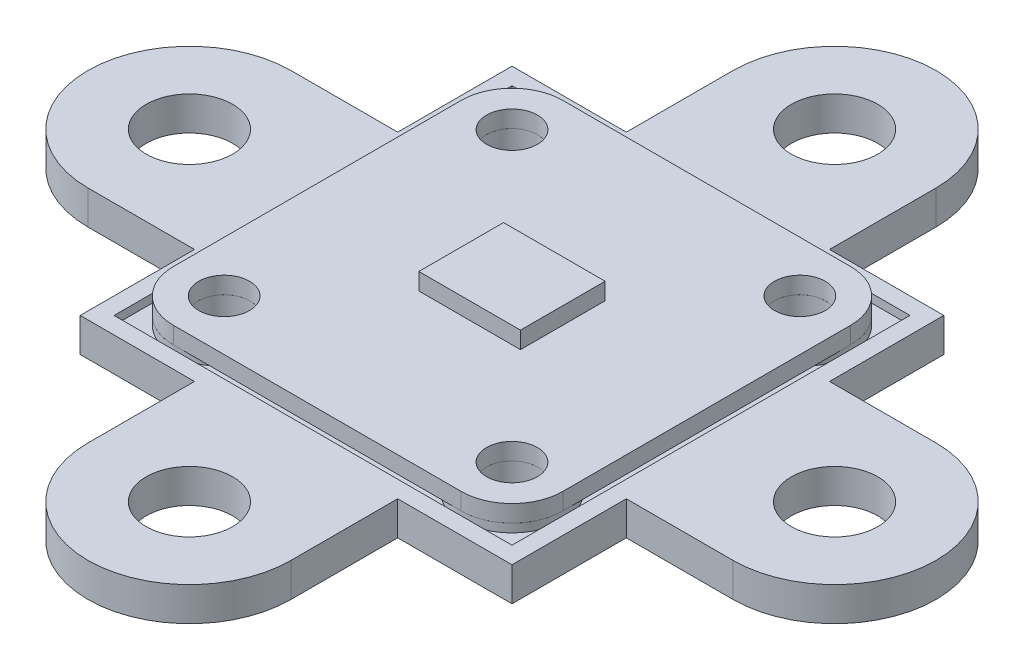
SolidWorks part; units mm, degrees
ref_plane "Front Plane" through (0, 0, 0) normal (0, 0, 1) x (1, 0, 0)
ref_plane "Top Plane" through (0, 0, 0) normal (0, 1, 0) x (1, 0, 0)
ref_plane "Right Plane" through (0, 0, 0) normal (1, 0, 0) x (0, 0, -1)
other "Bounding Box"
ref_plane "Default Plane" through (-8.9266, -12.7485, 0) normal (-0.1736, 0.9848, 0) x (0.9848, 0.1736, 0)
sketch "Sketch1" plane through (0, 0, 0) normal (0, 1, 0) x (1, 0, 0)
  line L1 (-11.5, -11.5) -> (11.5, -11.5)
  line L2 (-11.5, -11.5) -> (-11.5, 11.5)
  line L3 (-11.5, 11.5) -> (11.5, 11.5)
  line L4 (11.5, -11.5) -> (11.5, 11.5)
  line L5 (-11.5, -11.5) -> (11.5, 11.5) construction
  line L6 (-11.5, 11.5) -> (11.5, -11.5) construction
  line L7 (-8.5, 8.5) -> (8.5, 8.5) construction
  line L8 (-8.5, 8.5) -> (-8.5, -8.5) construction
  line L9 (-8.5, -8.5) -> (8.5, -8.5) construction
  line L10 (8.5, 8.5) -> (8.5, -8.5) construction
  line L11 (-8.5, 8.5) -> (8.5, -8.5) construction
  line L12 (-8.5, -8.5) -> (8.5, 8.5) construction
  circle A0 centre (-8.5, 8.5) radius 1.5
  circle A1 centre (8.5, 8.5) radius 1.5
  circle A2 centre (8.5, -8.5) radius 1.5
  circle A3 centre (-8.5, -8.5) radius 1.5
  point P0 (0, 0)
  point P6 (0, 0)
  dimension "D3" = 3
  dimension "D1" = 17
  dimension "D2" = 23
extrude "Boss-Extrude1" add sketch "Sketch1" along normal blind 1
sketch "Sketch2" plane through (0, 1, 0) normal (0, 1, 0) x (1, 0, 0)
  line L1 (-3, 2.5) -> (3, 2.5)
  line L2 (-3, 2.5) -> (-3, -2.5)
  line L3 (-3, -2.5) -> (3, -2.5)
  line L4 (3, 2.5) -> (3, -2.5)
  line L5 (-3, 2.5) -> (3, -2.5) construction
  line L6 (-3, -2.5) -> (3, 2.5) construction
  point P0 (0, 0)
  dimension "D1" = 5
  dimension "D2" = 6
extrude "Boss-Extrude2" add sketch "Sketch2" along normal blind 1
fillet "Fillet1" radius 3 4 edges at (-11.5, 0.5, -11.5) (11.5, 0.5, -11.5) (11.5, 0.5, 11.5) (-11.5, 0.5, 11.5)
sketch "Sketch3" plane through (0, 1, 0) normal (0, 1, 0) x (1, 0, 0)
  line L0 (-11.5, 8.5) -> (-11.5, -8.5) construction
  line L1 (-11.75, 11.75) -> (11.75, 11.75) construction
  line L2 (-11.75, 11.75) -> (-11.75, -11.75) construction
  line L3 (-11.75, -11.75) -> (11.75, -11.75) construction
  line L4 (11.75, 11.75) -> (11.75, -11.75) construction
  line L5 (-11.75, 11.75) -> (11.75, -11.75) construction
  line L6 (-11.75, -11.75) -> (11.75, 11.75) construction
  line L8 (-12.75, 12.75) -> (12.75, 12.75)
  line L9 (-12.75, 12.75) -> (-12.75, -12.75)
  line L10 (-12.75, -12.75) -> (12.75, -12.75)
  line L11 (12.75, 12.75) -> (12.75, -12.75)
  line L12 (-12.75, 12.75) -> (12.75, -12.75) construction
  line L13 (-12.75, -12.75) -> (12.75, 12.75) construction
  circle A0 centre (-8.5, 8.5) radius 1.5 construction
  circle A1 centre (8.5, 8.5) radius 1.5 construction
  circle A2 centre (8.5, -8.5) radius 1.5 construction
  circle A3 centre (-8.5, -8.5) radius 1.5 construction
  circle A4 centre (-8.5, 8.5) radius 1.5
  circle A5 centre (8.5, 8.5) radius 1.5
  circle A6 centre (8.5, -8.5) radius 1.5
  circle A7 centre (-8.5, -8.5) radius 1.5
  circle A8 centre (0, 0) radius 7.5
  point P12 (0, 0)
  point P20 (0, 0)
  dimension "D3" = 15
  dimension "D1" = 0.25
  dimension "D2" = 1
extrude "Boss-Extrude3" add sketch "Sketch3" along normal blind 1.5 from offset 3 separate body offset against normal yes
sketch "Sketch4" plane through (0, -2, 0) normal (0, -1, 0) x (1, 0, 0)
  circle A0 centre (-8.5, 8.5) radius 3
  circle A1 centre (-8.5, -8.5) radius 1.5
  circle A2 centre (-8.5, -8.5) radius 1.5
  circle A3 centre (8.5, -8.5) radius 1.5
  circle A4 centre (8.5, -8.5) radius 1.5
  circle A5 centre (8.5, 8.5) radius 1.5
  circle A6 centre (8.5, 8.5) radius 1.5
  circle A7 centre (-8.5, 8.5) radius 1.5
  circle A8 centre (-8.5, 8.5) radius 1.5
  circle A9 centre (8.5, 8.5) radius 3
  circle A10 centre (8.5, -8.5) radius 3
  circle A11 centre (-8.5, -8.5) radius 3
  arc A12 (-8.5, 11.5) -> (-11.5, 8.5) centre (-8.5, 8.5) ccw construction
  dimension "D1" = 0
  dimension "D2" = 0
  dimension "D3" = 0
  dimension "D4" = 0
extrude "Boss-Extrude4" add sketch "Sketch4" against normal up to surface (2 mm away) up to face at (8.5, 0, 10)
sketch "Sketch5" plane through (0, -2, 0) normal (0, -1, 0) x (1, 0, 0)
  line L0 (11.75, -11.75) -> (11.75, 11.75) construction
  line L1 (-11.75, 11.75) -> (11.75, 11.75) construction
  line L2 (-11.75, -11.75) -> (-11.75, 11.75) construction
  line L3 (-11.75, -11.75) -> (11.75, -11.75) construction
  line L4 (-12.75, -12.75) -> (12.75, -12.75) construction
  line L5 (12.75, -12.75) -> (12.75, 12.75) construction
  line L6 (-12.75, 12.75) -> (12.75, 12.75) construction
  line L7 (-12.75, -12.75) -> (-12.75, 12.75) construction
  line L8 (11.75, -11.75) -> (11.75, 11.75)
  line L9 (-11.75, 11.75) -> (11.75, 11.75)
  line L10 (-11.75, -11.75) -> (-11.75, 11.75)
  line L11 (-11.75, -11.75) -> (11.75, -11.75)
  line L12 (-12.75, -12.75) -> (12.75, -12.75)
  line L13 (12.75, -12.75) -> (12.75, 12.75)
  line L14 (-12.75, 12.75) -> (12.75, 12.75)
  line L15 (-12.75, -12.75) -> (-12.75, 12.75)
extrude "Boss-Extrude5" add sketch "Sketch5" against normal blind 2
sketch "Sketch6" plane through (0, 0, 0) normal (0, 1, 0) x (-1, 0, 0)
  line L0 (0, -19.05) -> (0, 0) construction
  line L1 (-6, -19.05) -> (-6, -12.75)
  line L2 (12.75, -12.75) -> (-12.75, -12.75) construction
  line L3 (-6, -12.75) -> (6, -12.75)
  line L4 (6, -12.75) -> (6, -19.05)
  circle A0 centre (0, -19.05) radius 2.5527
  arc A1 (-6, -19.05) -> (6, -19.05) centre (0, -19.05) ccw
  point P6 (5.4839, -21.4846)
  point P10 (6.0256, -19.3119)
  point P12 (-6.0313, -19.05)
  point P13 (-5.9233, -18.958)
  dimension "D2" = 5.1054
  dimension "D3" = 6
  dimension "D1" = 19.05
extrude "Boss-Extrude6" add sketch "Sketch6" against normal blind 2
ref_axis "Axis1" through (0, -0.175, 0) along (0, 1, 0)
pattern_circular "CirPattern1" count 4 over 360 about axis through (0, -0.175, 0) along (0, 1, 0) of "Boss-Extrude6"
